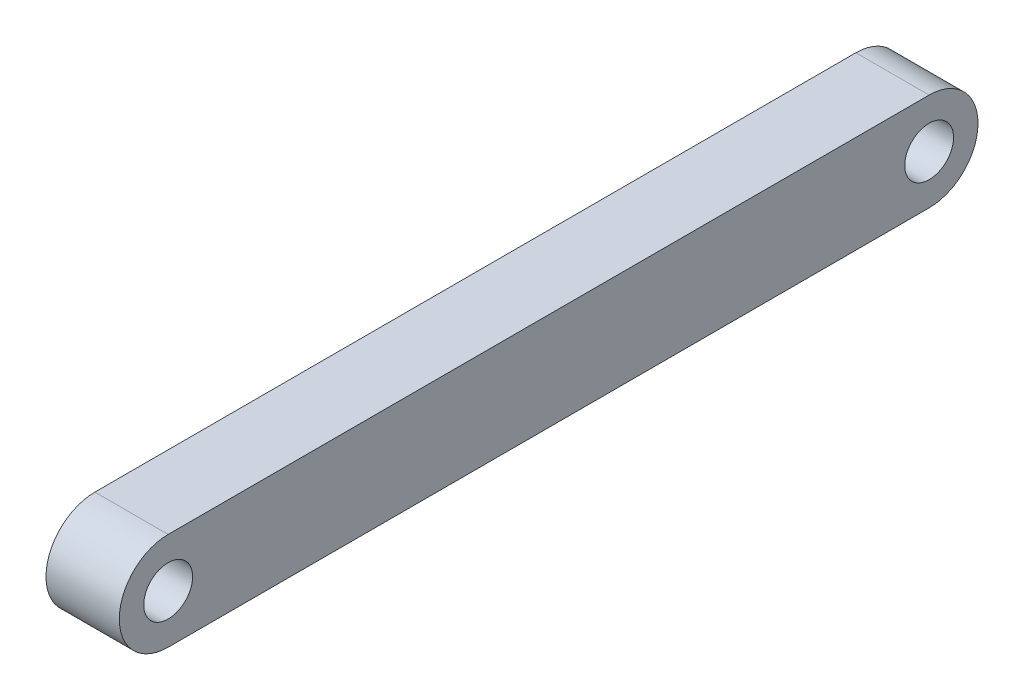
SolidWorks part; units mm, degrees
ref_plane "Front Plane" through (0, 0, 0) normal (0, 0, 1) x (1, 0, 0)
ref_plane "Top Plane" through (0, 0, 0) normal (0, 1, 0) x (1, 0, 0)
ref_plane "Right Plane" through (0, 0, 0) normal (1, 0, 0) x (0, 0, -1)
sketch "Sketch1" plane through (0, 0, 0) normal (1, 0, 0) x (0, 0, -1)
  line L4 (-15.575, -2) -> (15.575, -2)
  line L6 (-15.575, 2) -> (15.575, 2)
  line L8 (-15.575, -2) -> (15.575, 2) construction
  line L9 (-15.575, 2) -> (15.575, -2) construction
  arc A4 (15.575, 2) -> (15.575, -2) centre (15.575, 0) cw
  arc A5 (-15.575, 2) -> (-15.575, -2) centre (-15.575, 0) ccw
  circle A6 centre (-15.575, 0) radius 1
  circle A7 centre (15.575, 0) radius 1
  point P0 (0, 0)
  point P1 (0, 0)
  dimension "D2" = 4
  dimension "D3" = 2
  dimension "D1" = 31.15
extrude "Boss-Extrude1" add sketch "Sketch1" along normal mid plane 3
